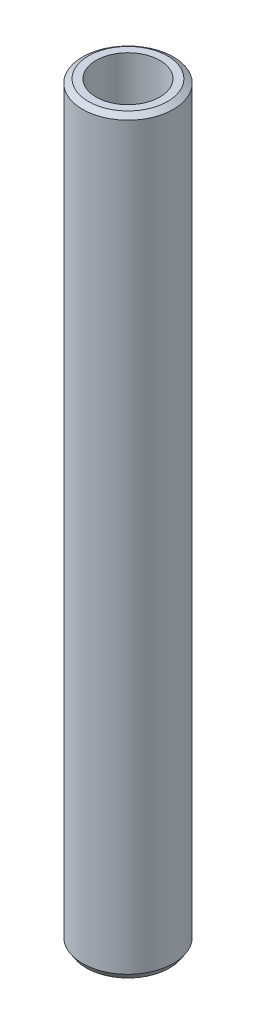
SolidWorks part; units mm, degrees
ref_plane "Front Plane" through (0, 0, 0) normal (0, 0, 1) x (1, 0, 0)
ref_plane "Top Plane" through (0, 0, 0) normal (0, 1, 0) x (1, 0, 0)
ref_plane "Right Plane" through (0, 0, 0) normal (1, 0, 0) x (0, 0, -1)
sketch "Sketch1" plane through (0, 0, 0) normal (0, 1, 0) x (1, 0, 0)
  circle A0 centre (0, 0) radius 30
  dimension "SHAFT_OD" = 60
extrude "Boss-Extrude1" add sketch "Sketch1" along normal blind 494.562
sketch "Sketch2" plane through (0, 0, 0) normal (0, 1, 0) x (1, 0, 0)
  circle A0 centre (0, 0) radius 21.0183
  dimension "BORE_D" = 42.0366
extrude "Cut-Extrude1" cut sketch "Sketch2" along normal through all
chamfer "Chamfer1" distance 2.5193 angle 57.095 2 edges at (0, 494.562, 30) (0, 0, 30) first distance on face at (0, 494.562, 30) first distance on face at (0, 0, 21.0183)
